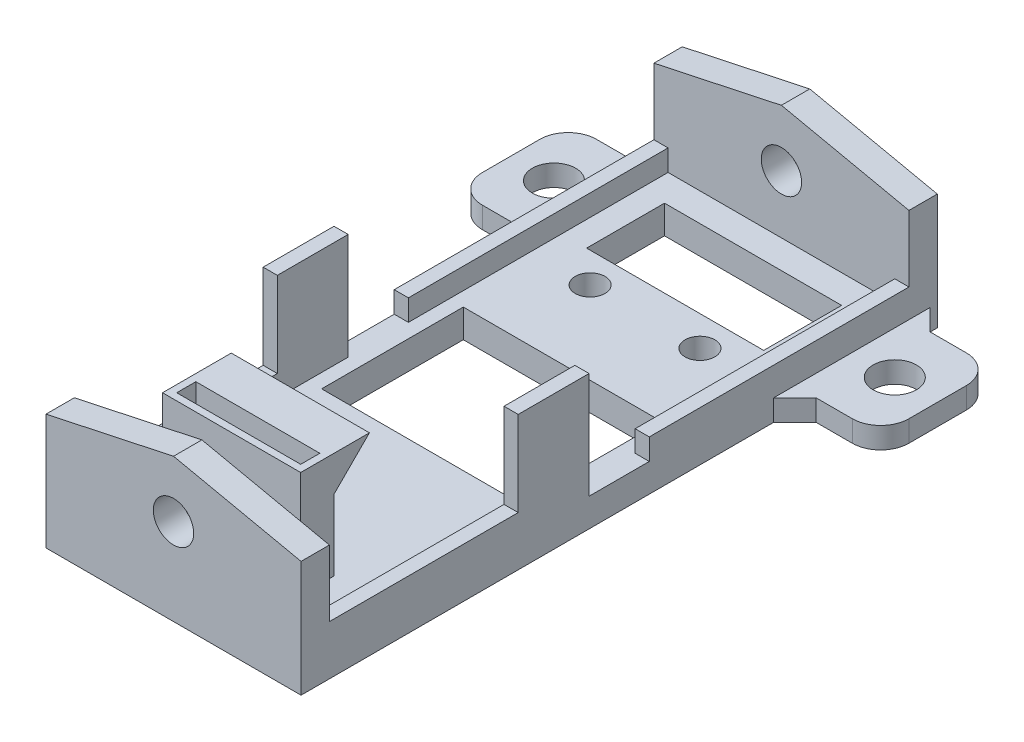
SolidWorks part; units mm, degrees
ref_plane "Front Plane" through (0, 0, 0) normal (0, 0, 1) x (1, 0, 0)
ref_plane "Top Plane" through (0, 0, 0) normal (0, 1, 0) x (1, 0, 0)
ref_plane "Right Plane" through (0, 0, 0) normal (1, 0, 0) x (0, 0, -1)
sketch "Sketch1" plane through (0, 0, 0) normal (0, 0, 1) x (1, 0, 0)
  line L3 (-18, 114.7896) -> (0, 114.7896)
  line L4 (0, 114.7896) -> (18, 114.7896)
  line L7 (0, 118.6383) -> (-40.4, 110) construction
  line L9 (38.0273, 110.5073) -> (0, 118.6383) construction
  line L11 (18, 114.7896) -> (18, 121.7896)
  line L12 (18, 121.7896) -> (16, 121.7896)
  line L13 (16, 121.7896) -> (16, 118.7896)
  line L14 (16, 118.7896) -> (-16, 118.7896)
  line L15 (-16, 118.7896) -> (-16, 121.7896)
  line L16 (-16, 121.7896) -> (-18, 121.7896)
  line L17 (-18, 121.7896) -> (-18, 114.7896)
  point P15 (0, 118.7896)
  dimension "D1" = 32
  dimension "D2" = 2
  dimension "D3" = 3
  dimension "D4" = 4
extrude "Boss-Extrude1" add sketch "Sketch1" along normal up to surface (89.8 mm away)
sketch "Sketch2" plane through (0, 114.7896, 0) normal (0, -1, 0) x (1, 0, 0)
  line L0 (18, 89.8) -> (18, 0) construction
  line L5 (-14, 54.9) -> (14, 54.9)
  line L6 (-14, 54.9) -> (-14, 34.9)
  line L7 (-14, 34.9) -> (14, 34.9)
  line L8 (14, 54.9) -> (14, 34.9)
  point P4 (0, 34.9)
  point P8 (18, 44.9)
  point P9 (14, 44.9)
  dimension "D1" = 4
  dimension "D2" = 20
extrude "Cut-Extrude1" cut sketch "Sketch2" against normal up to next
sketch "Sketch3" plane through (-18, 0, 0) normal (-1, 0, 0) x (0, 0, 1)
  line L0 (89.8, 121.7896) -> (0, 121.7896) construction
  line L1 (40.65, 118.7896) -> (49.15, 118.7896)
  line L2 (40.65, 118.7896) -> (40.65, 121.7896)
  line L3 (40.65, 121.7896) -> (49.15, 121.7896)
  line L4 (49.15, 118.7896) -> (49.15, 121.7896)
  line L5 (89.8, 118.7896) -> (0, 118.7896) construction
  point P9 (44.9, 121.7896)
  point P10 (44.9, 121.7896)
  dimension "D1" = 8.5
extrude "Cut-Extrude2" cut sketch "Sketch3" against normal through all
sketch "Sketch4" plane through (0, 118.7896, 0) normal (0, 1, 0) x (1, 0, 0)
  circle A0 centre (7.75, -23.25) radius 2.1 construction
  circle A4 centre (-7.75, -23.25) radius 2.1 construction
  circle A5 centre (7.75, -23.25) radius 2.1
  circle A6 centre (-7.75, -23.25) radius 2.1
extrude "Cut-Extrude3" cut sketch "Sketch4" against normal through all
ref_plane "Plane2" through (0, 0, 44.9) normal (0, 0, -1) x (-1, 0, 0)
sketch "Sketch5" plane through (0, 0, 0) normal (0, 0, 1) x (1, 0, 0)
  line L0 (-18, 114.7896) -> (-18, 131.1512)
  line L1 (-56.4, 122.9405) -> (0, 135) construction
  line L2 (-18, 131.1512) -> (0, 135)
  line L3 (0, 135) -> (18, 131.1512)
  line L4 (0, 135) -> (56.4, 122.9405) construction
  line L5 (18, 131.1512) -> (18, 114.7896)
  line L6 (18, 114.7896) -> (-18, 114.7896)
  line L7 (0.6273, 134.8659) -> (54.0273, 123.4479) construction
  line L8 (-54.0273, 123.4479) -> (-0.6273, 134.8659) construction
  circle A0 centre (0, 127) radius 2.85
  dimension "D1" = 5.7
  dimension "D2" = 8
extrude "Boss-Extrude2" add sketch "Sketch5" along normal blind 4
mirror "Mirror1" about plane through (0, 0, 44.9) normal (0, 0, -1) of "Boss-Extrude2"
sketch "Sketch6" plane through (0, 118.7896, 0) normal (0, 1, 0) x (1, 0, 0)
  line L1 (12.5, -19) -> (-12.5, -19)
  line L2 (12.5, -19) -> (12.5, -8)
  line L3 (12.5, -8) -> (-12.5, -8)
  line L4 (-12.5, -19) -> (-12.5, -8)
  point P4 (0, -8)
  dimension "D1" = 11
  dimension "D2" = 25
  dimension "D3" = 8
extrude "Cut-Extrude4" cut sketch "Sketch6" against normal through all
sketch "Sketch8" plane through (0, 118.7896, 0) normal (0, 1, 0) x (1, 0, 0)
  line L0 (16, -85.8) -> (-16, -85.8) construction
  line L1 (8.75, -80.6) -> (-8.75, -80.6)
  line L2 (8.75, -80.6) -> (8.75, -77.9)
  line L3 (8.75, -77.9) -> (-8.75, -77.9)
  line L4 (-8.75, -80.6) -> (-8.75, -77.9)
  line L5 (0, -89.8) -> (53.4, -89.8) construction
  line L6 (9.75, -76.9) -> (-9.75, -76.9)
  line L7 (-9.75, -81.6) -> (-9.75, -76.9)
  line L8 (9.75, -81.6) -> (-9.75, -81.6)
  line L9 (9.75, -81.6) -> (9.75, -76.9)
  point P6 (0, -85.8)
  point P7 (0, -80.6)
  dimension "D1" = 8.2
  dimension "D2" = 2.7
  dimension "D3" = 17.5
  dimension "D4" = 1
extrude "Boss-Extrude3" add sketch "Sketch8" along normal blind 15
sketch "Sketch9" plane through (-9.75, 0, 0) normal (-1, 0, 0) x (0, 0, 1)
  line L0 (76.9, 128.7896) -> (71.9, 133.7896)
  line L1 (76.9, 133.7896) -> (76.9, 118.7896) construction
  line L2 (71.9, 133.7896) -> (76.9, 133.7896)
  line L3 (76.9, 133.7896) -> (76.9, 128.7896)
  dimension "D1" = 5
  dimension "D2" = 45
extrude "Boss-Extrude4" add sketch "Sketch9" against normal up to surface (19.5 mm away) up to face at (9.75, 126.2896, 79.25)
sketch "Sketch13" plane through (0, 118.7896, 0) normal (0, 1, 0) x (1, 0, 0)
  line L4 (-8.75, -80.6) -> (8.75, -80.6)
  line L5 (8.75, -80.6) -> (8.75, -77.9)
  line L6 (8.75, -77.9) -> (-8.75, -77.9)
  line L7 (-8.75, -77.9) -> (-8.75, -80.6)
  line L8 (-8.75, -80.6) -> (8.75, -80.6)
  line L9 (8.75, -80.6) -> (8.75, -77.9)
  line L10 (8.75, -77.9) -> (-8.75, -77.9)
  line L11 (-8.75, -77.9) -> (-8.75, -80.6)
  dimension "D1" = 0
extrude "Cut-Extrude5" cut sketch "Sketch13" against normal through all
sketch "Sketch10" plane through (0, 121.7896, 0) normal (0, 1, 0) x (1, 0, 0)
  line L1 (16, -59.15) -> (18, -59.15)
  line L2 (16, -59.15) -> (16, -49.15)
  line L3 (16, -49.15) -> (18, -49.15)
  line L4 (18, -59.15) -> (18, -49.15)
  line L5 (0, -1000) -> (0, 49000) construction
  line L6 (-16, -49.15) -> (-18, -49.15)
  line L7 (-16, -59.15) -> (-16, -49.15)
  line L8 (-16, -59.15) -> (-18, -59.15)
  line L9 (-18, -59.15) -> (-18, -49.15)
  dimension "D1" = 10
extrude "Boss-Extrude5" add sketch "Sketch10" along normal up to surface (12 mm away)
sketch "Sketch14" plane through (0, 114.7896, 0) normal (0, 1, 0) x (1, 0, 0)
  line L0 (-18, -40.65) -> (-18, -4) construction
  line L1 (-18, -4) -> (-30.1, -4)
  line L2 (-18, -4) -> (-18, -20.1)
  line L3 (-18, -20.1) -> (-30.1, -20.1)
  line L4 (-30.1, -4) -> (-30.1, -20.1)
  circle A0 centre (-24.05, -12.05) radius 3.05
  point P9 (-30.1, -12.05)
  point P10 (-24.05, -20.1)
  dimension "D1" = 6.1
  dimension "D2" = 3
  dimension "D3" = 5
extrude "Boss-Extrude7" add sketch "Sketch14" along normal blind 3
mirror "Mirror2" about plane through (0, 0, 0) normal (1, 0, 0) of "Boss-Extrude7"
fillet "Fillet1" radius 4 4 edges at (-30.1, 116.2896, 4) (-30.1, 116.2896, 20.1) (30.1, 116.2896, 4) (30.1, 116.2896, 20.1)
chamfer "Chamfer1" distance 3 angle 45 4 edges at (-18, 116.2896, 20.1) (-18, 116.2896, 4) (18, 116.2896, 4) (18, 116.2896, 20.1)
sketch "Sketch17" plane through (0, 118.7896, 0) normal (0, 1, 0) x (1, 0, 0)
  circle A0 centre (0, -71.9) radius 2.1
  circle A1 centre (0, -71.9) radius 2.85 construction
  dimension "D1" = 4.2
extrude "Cut-Extrude6" cut sketch "Sketch17" against normal through all
equation "\"width\"= 24"
equation "\"thk\"= 3"
equation "\"holesize\"= 4.2"
equation "\"holedistance\"= ( 20 + 12 ) / 2"
equation "\"threaded_hole\"= 3.9"
equation "\"fillet_radius\"= 2"
equation "\"ground_clearance\"= 25"
equation "\"tire_thk\"= 3"
equation "\"innerwheel_diam\" = \"wheel_diam\"-2*\"tire_thk\""
equation "\"innerwheel_thk\"= 8"
equation "\"wheel_diam\"= 2*(\"width\"/2+\"ground_clearance\")"
equation "\"coloursensor_holesize\"= 2.65"
equation "\"hole_to_edge\" = 4"
equation "\"D1@Sketch5\"=\"M4_insert_diam\""
equation "\"D1@Sketch17\"=\"holesize\""
equation "\"M4_insert_diam\"= 5.7"
